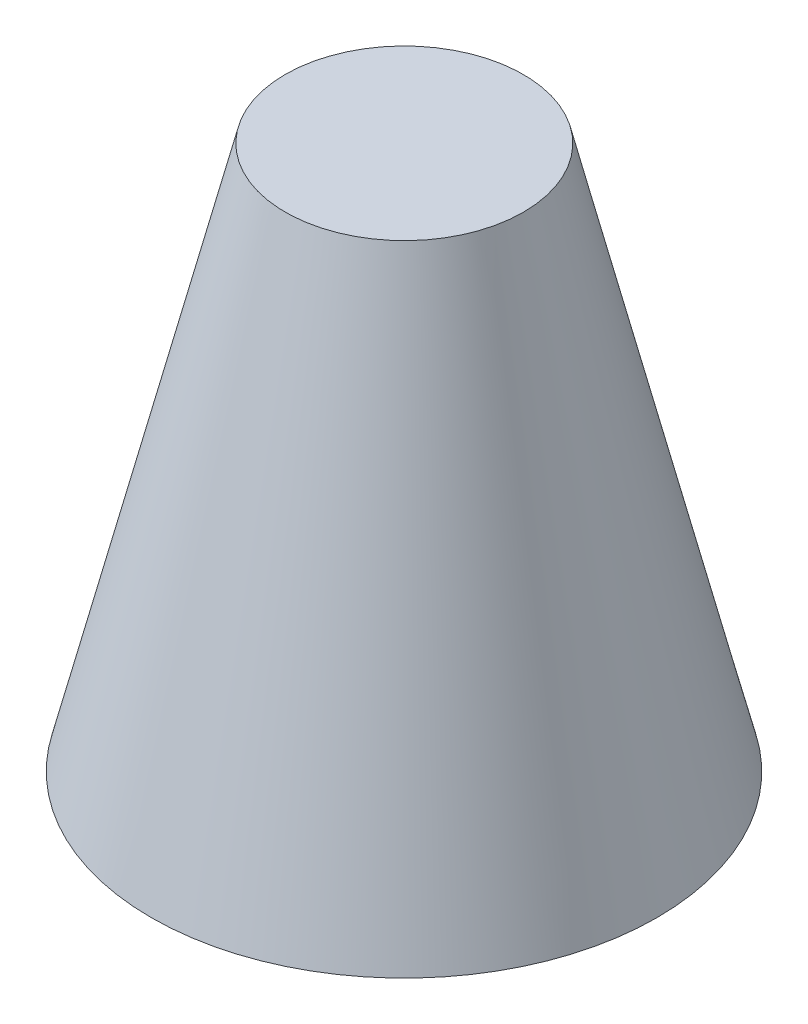
SolidWorks part; units mm, degrees
ref_plane "Front Plane" through (0, 0, 0) normal (0, 0, 1) x (1, 0, 0)
ref_plane "Top Plane" through (0, 0, 0) normal (0, 1, 0) x (1, 0, 0)
ref_plane "Right Plane" through (0, 0, 0) normal (1, 0, 0) x (0, 0, -1)
sketch "Sketch1" plane through (0, 0, 0) normal (0, 0, 1) x (1, 0, 0)
  line L0 (127, 271.5) -> (635, 271.5) construction
  line L1 (302.9775, 5.0506) -> (311.054, 37.81)
  line L2 (311.054, 37.81) -> (317.996, 37.81)
  line L3 (317.9877, 23.109) -> (308.991, 23.109)
  line L4 (317.996, 37.81) -> (317.9775, 5.0506) construction
  line L5 (308.991, 23.109) -> (304.5389, 5.0506)
  line L6 (304.5389, 5.0506) -> (302.9775, 5.0506)
  line L7 (317.996, 37.81) -> (317.9877, 23.109)
revolve "Revolve1" add sketch "Sketch1" angle 360 about L4
ref_plane "Plane1" through (0.0215, 37.9857, 0) normal (0.0006, 1, 0) x (1, -0.0006, 0)
sketch "Sketch2" plane through (0.0215, 37.9857, 0) normal (0.0006, 1, 0) x (1, -0.0006, 0)
  circle A0 centre (317.9746, 0) radius 7.6387
extrude "Cut-Extrude2" cut sketch "Sketch2" against normal blind 0.5 and the other way blind 0.5
